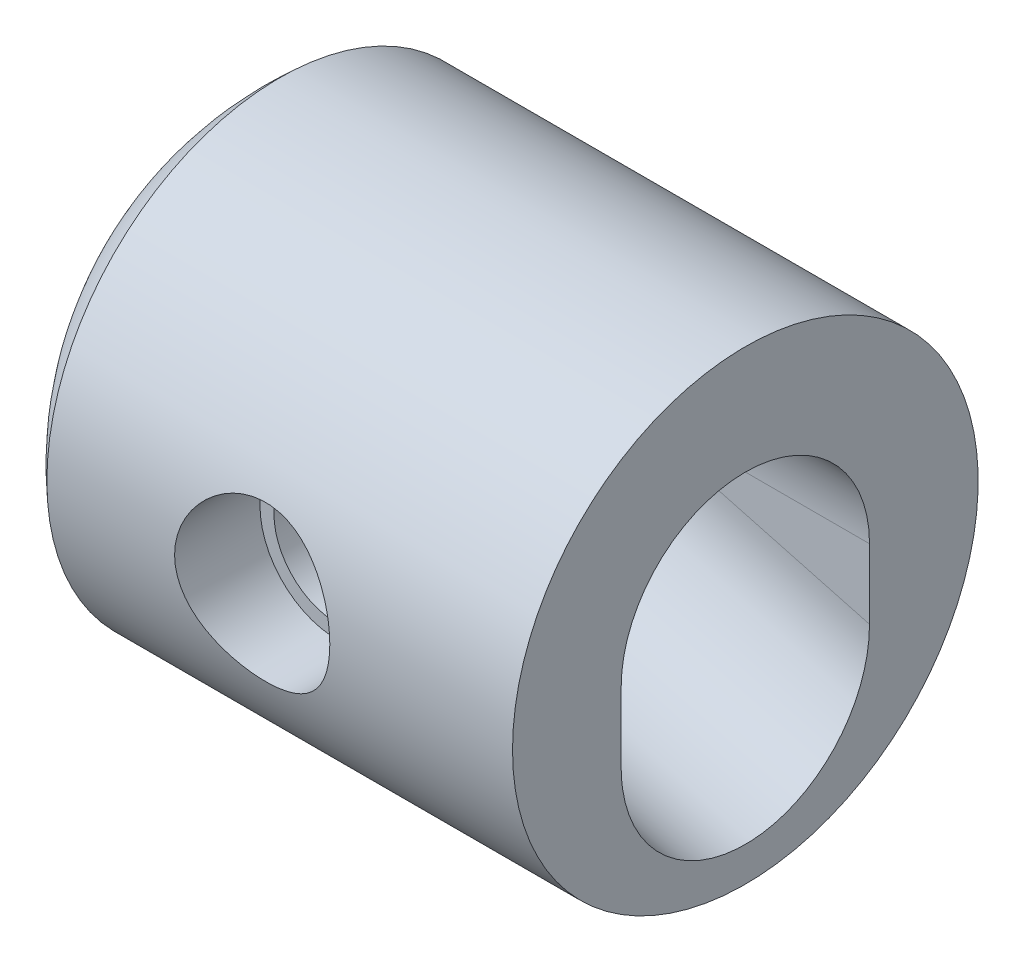
SolidWorks part; units mm, degrees
material "1.4301 (X5CrNi18-10)"
ref_plane "Vorne" through (0, 0, 0) normal (0, 0, 1) x (1, 0, 0)
ref_plane "Oben" through (0, 0, 0) normal (0, 1, 0) x (1, 0, 0)
ref_plane "Rechts" through (0, 0, 0) normal (1, 0, 0) x (0, 0, -1)
sketch "Skizze3" plane through (0, 0, 0) normal (0, 1, 0) x (1, 0, 0)
  line L0 (-18.3303, 8) -> (-50, 8)
  line L1 (-16.5, 0) -> (16.5, 0) construction
  line L2 (0, -16.5) -> (0, 16.5) construction
  line L3 (-13.2288, 15) -> (16.7712, 15)
  circle A0 centre (0, 0) radius 20
  dimension "D1" = 40
  dimension "D2" = 8
  dimension "D3" = 50
  dimension "D4" = 15
  dimension "D5" = 30
sketch "Skizze4" plane through (0, 0, 0) normal (0, 1, 0) x (1, 0, 0)
  line L0 (-13.2288, 15) -> (16.7712, 15) construction
  line L1 (-13.2288, 15) -> (16.7712, 15)
  line L2 (-18.3303, 8) -> (16.7712, 8)
  line L4 (16.7712, 8) -> (16.7712, 15)
  line L5 (-18.3303, 8) -> (-50, 8) construction
  line L6 (-20, 0) -> (20, 0) construction
  line L7 (-16.5, 0) -> (16.5, 0) construction
  circle A0 centre (0, 0) radius 20 construction
  arc A1 (-13.2288, 15) -> (-18.3303, 8) centre (0, 0) ccw
revolve "Rotation1" add sketch "Skizze4" angle 360 about L6
sketch "Skizze6" plane through (0, 0, 0) normal (0, 1, 0) x (1, 0, 0)
  line L0 (-13.2288, 15) -> (16.7712, 15) construction
  line L1 (-4.1, 9.5) -> (-4.1, -9.5)
  line L3 (0, -16.5) -> (0, 16.5) construction
  line L4 (0, 15) -> (0, -15) construction
  line L5 (-5, 15) -> (0, 15)
  line L6 (0, 15) -> (0, -15)
  line L7 (0, -15) -> (-5, -15)
  line L8 (-4.1, 9.5) -> (-5, 9.5)
  line L9 (-5, 9.5) -> (-5, 15)
  line L10 (-4.1, -9.5) -> (-5, -9.5)
  line L11 (-5, -9.5) -> (-5, -15)
  line L12 (16.7712, 8) -> (-18.3303, 8) construction
  line L13 (-18.3303, -8) -> (16.7712, -8) construction
  line L14 (-13.2288, -15) -> (16.7712, -15) construction
  dimension "D1" = 4.1
  dimension "D2" = 1.5
  dimension "D3" = 1.5
  dimension "D4" = 5
revolve "Schnitt-Rotation1" cut sketch "Skizze6" angle 360 about L4
ref_axis "Achse1" through (0, 0, 16.5) along (0, 0, -1)
sketch "Skizze7" plane through (0, 0, 0) normal (0, 0, 1) x (1, 0, 0)
  line L0 (0, 0) -> (4.0192, 15)
  line L1 (16.7712, 15) -> (-13.2288, 15) construction
  line L2 (0, -16.5) -> (0, 16.5) construction
  dimension "D1" = 15
ref_plane "Ebene1" through (0, 0, 0) normal (0.9659, -0.2588, 0) x (0, 0, -1)
sketch "Skizze8" plane through (0, 0, 0) normal (0.9659, -0.2588, 0) x (0, 0, -1)
  circle A0 centre (0, 0) radius 8
  dimension "D1" = 16
extrude "Schnitt-Linear austragen1" cut sketch "Skizze8" against normal through all and the other way through all
sketch "Skizze9" plane through (0, 0, 0) normal (0, 0, 1) x (1, 0, 0)
  line L0 (-18.3303, 2.4132) -> (-15.6352, 12.4716) construction
  line L1 (-17.7057, 4.7442) -> (-3.9603, 1.0612)
  line L2 (-4.1, 0) -> (-18.3303, 0)
  line L4 (-18.3303, -8) -> (-18.3303, 2.4132) construction
  line L5 (-18.3303, 2.4132) -> (-17.7057, 4.7442)
  line L6 (-18.3303, 0) -> (-18.3303, 2.4132)
  line L7 (16.7712, -15) -> (16.7712, 15) construction
  line L8 (16.7712, -4.4938) -> (16.7712, 0)
  line L9 (16.7712, -4.4938) -> (3.9603, -1.0612)
  line L10 (4.1, 0) -> (16.7712, 0)
  circle A2 centre (0, 0) radius 4.1 construction
  arc A3 (-3.9603, 1.0612) -> (-4.1, 0) centre (0, 0) ccw
  arc A4 (3.9603, -1.0612) -> (4.1, 0) centre (0, 0) ccw
extrude "Schnitt-Linear austragen2" cut sketch "Skizze9" against normal blind 8 and the other way blind 8
equation "\"D3@Skizze6\"=\"D2@Skizze6\""
